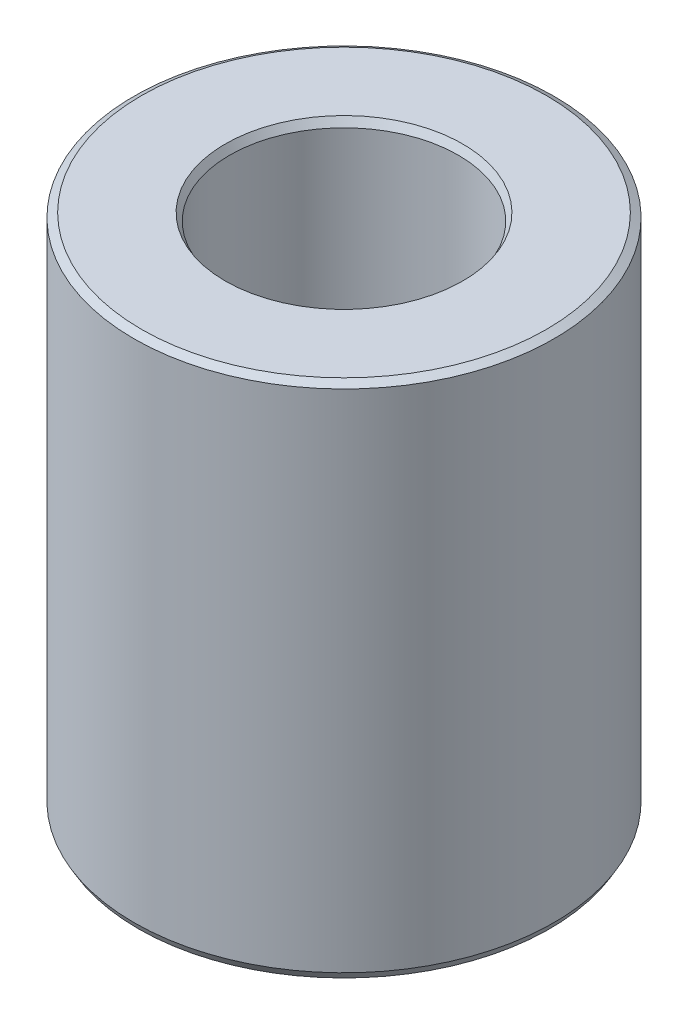
SolidWorks part; units mm, degrees
ref_plane "Front Plane" through (0, 0, 0) normal (0, 0, 1) x (1, 0, 0)
ref_plane "Top Plane" through (0, 0, 0) normal (0, 1, 0) x (1, 0, 0)
ref_plane "Right Plane" through (0, 0, 0) normal (1, 0, 0) x (0, 0, -1)
sketch "Sketch1" plane through (0, 0, 0) normal (0, 1, 0) x (1, 0, 0)
  circle A0 centre (0, 0) radius 17.5
  dimension "SLEEVE_OD" = 35
extrude "Boss-Extrude1" add sketch "Sketch1" along normal blind 43.1106
sketch "Sketch2" plane through (0, 0, 0) normal (0, 1, 0) x (1, 0, 0)
  circle A0 centre (0, 0) radius 9.5315
  dimension "BORE_D" = 19.063
extrude "Cut-Extrude1" cut sketch "Sketch2" along normal through all
chamfer "Chamfer1" distance 0.3614 angle 60.181 4 edges at (0, 43.1106, 9.5315) (0, 0, 9.5315) (0, 0, 17.5) (0, 43.1106, 17.5) first distance on face at (0, 43.1106, 9.5315) first distance on face at (0, 0, 9.5315) first distance on face at (0, 43.1106, 17.5)
